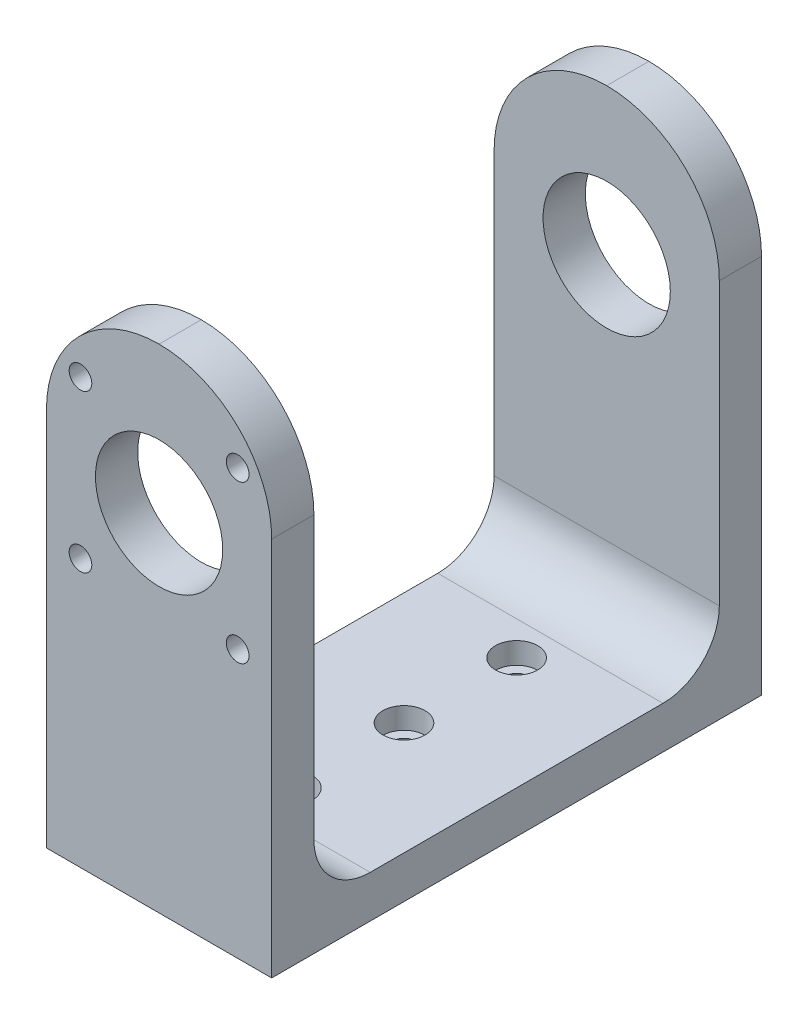
SolidWorks part; units mm, degrees
ref_plane "Front Plane" through (0, 0, 0) normal (0, 0, 1) x (1, 0, 0)
ref_plane "Top Plane" through (0, 0, 0) normal (0, 1, 0) x (1, 0, 0)
ref_plane "Right Plane" through (0, 0, 0) normal (1, 0, 0) x (0, 0, -1)
sketch "Sketch1" plane through (0, 0, 0) normal (0, 1, 0) x (1, 0, 0)
  line L1 (0, 0) -> (50.8, 0)
  line L2 (0, 0) -> (0, 110.49)
  line L3 (0, 110.49) -> (50.8, 110.49)
  line L4 (50.8, 0) -> (50.8, 110.49)
  dimension "D1" = 50.8
  dimension "D2" = 110.49
extrude "Boss-Extrude1" add sketch "Sketch1" along normal blind 9.525 contours L2 L1 L4 L3
sketch "Sketch2" plane through (0, 9.525, 0) normal (0, 1, 0) x (1, 0, 0)
  line L0 (0, 0) -> (0, 110.49) construction
  line L1 (50.8, 110.49) -> (0, 110.49)
  line L2 (50.8, 110.49) -> (50.8, 100.965)
  line L3 (50.8, 100.965) -> (0, 100.965)
  line L4 (0, 110.49) -> (0, 100.965)
  dimension "D1" = 9.525
extrude "Boss-Extrude2" add sketch "Sketch2" along normal blind 101.6 contours L2 L1 L4 L3
sketch "Sketch3" plane through (0, 9.525, 0) normal (0, 1, 0) x (1, 0, 0)
  line L0 (50.8, 0) -> (50.8, 100.965) construction
  line L1 (0, 0) -> (50.8, 0)
  line L2 (0, 0) -> (0, 9.525)
  line L3 (0, 9.525) -> (50.8, 9.525)
  line L4 (50.8, 0) -> (50.8, 9.525)
  dimension "D1" = 9.525
extrude "Boss-Extrude3" add sketch "Sketch3" along normal blind 101.6
sketch "Sketch8" plane through (0, 0, 0) normal (0, 0, 1) x (1, 0, 0)
  line L0 (0, 111.125) -> (50.8, 111.125) construction
  circle A0 centre (25.4, 78.105) radius 14.351
  dimension "D1" = 28.702
  dimension "D2" = 33.02
extrude "Cut-Extrude7" cut sketch "Sketch8" against normal through all contours A0
sketch "Sketch9" plane through (0, 0, -9.525) normal (0, 0, -1) x (-1, 0, 0)
  line L0 (-43.1292, 95.8342) -> (-7.6708, 60.3758) construction
  circle A0 centre (-43.1292, 95.8342) radius 2.5527
  circle A1 centre (-7.6708, 95.8342) radius 2.5527
  circle A2 centre (-7.6708, 60.3758) radius 2.5527
  circle A3 centre (-43.1292, 60.3758) radius 2.5527
  circle A4 centre (-25.4, 78.105) radius 14.351 construction
  point P2 (0, 0)
  point P11 (0, 0)
  point P12 (0, 0)
  dimension "D1" = 35.4584
  dimension "D2" = 35.4584
  dimension "D3" = 35.4584
  dimension "D4" = 5.1054
  dimension "D5" = 17.7292
  dimension "D6" = 17.7292
extrude "Cut-Extrude8" cut sketch "Sketch9" against normal through all
sketch "Sketch10" plane through (0, 0, -110.49) normal (0, 0, -1) x (-1, 0, 0)
  circle A0 centre (-43.1292, 95.8342) radius 2.5527
  circle A1 centre (-7.6708, 95.8342) radius 2.5527
  circle A2 centre (-7.6708, 60.3758) radius 2.5527
  circle A3 centre (-43.1292, 60.3758) radius 2.5527
  circle A4 centre (-7.6708, 60.3758) radius 2.5527 construction
  circle A5 centre (-7.6708, 95.8342) radius 2.5527 construction
  circle A6 centre (-43.1292, 60.3758) radius 2.5527 construction
  circle A7 centre (-43.1292, 95.8342) radius 2.5527 construction
  point P0 (0, 0)
  dimension "D1" = 5.1054
extrude "Cut-Extrude9" cut sketch "Sketch10" against normal blind 6.35
fillet "Fillet5" radius 25.4 1 edges at (0, 111.125, -4.7625)
fillet "Fillet6" radius 25.4 1 edges at (50.8, 111.125, -4.7625)
fillet "Fillet7" radius 25.4 1 edges at (0, 111.125, -105.7275)
fillet "Fillet8" radius 25.4 1 edges at (50.8, 111.125, -105.7275)
sketch "Sketch11" plane through (0, 9.525, 0) normal (0, 1, 0) x (1, 0, 0)
  line L1 (50.8, 9.525) -> (50.8, 100.965) construction
  line L2 (50.8, 100.965) -> (0, 100.965) construction
  circle A0 centre (25.4, 55.245) radius 2.5527
  point P2 (0, 0)
  point P3 (0, 0)
  point P5 (0, 0)
  point P6 (0, 0)
  point P7 (34.4737, 36.6434)
  point P9 (50.8, 55.245)
  point P12 (25.4, 100.965)
  dimension "D1" = 5.1054
  dimension "D2" = 0
  dimension "D3" = 0
extrude "Cut-Extrude10" cut sketch "Sketch11" against normal through all
sketch "Sketch12" plane through (0, 9.525, 0) normal (0, 1, 0) x (1, 0, 0)
  circle A0 centre (25.4, 29.845) radius 2.54
  circle A1 centre (25.4, 55.245) radius 2.5527 construction
  circle A2 centre (25.4, 80.645) radius 2.54
  dimension "D1" = 25.4
  dimension "D2" = 25.4
extrude "Cut-Extrude11" cut sketch "Sketch12" against normal through all
fillet "Fillet9" radius 12.7 2 edges at (25.4, 9.525, -9.525) (25.4, 9.525, -100.965)
sketch "Sketch13" plane through (0, 9.525, 0) normal (0, 1, 0) x (1, 0, 0)
  circle A0 centre (25.4, 55.245) radius 4.7625
  circle A1 centre (25.4, 29.845) radius 4.7625
  circle A3 centre (25.4, 80.645) radius 4.7625
  dimension "D1" = 9.525
extrude "Cut-Extrude12" cut sketch "Sketch13" against normal blind 4.826
